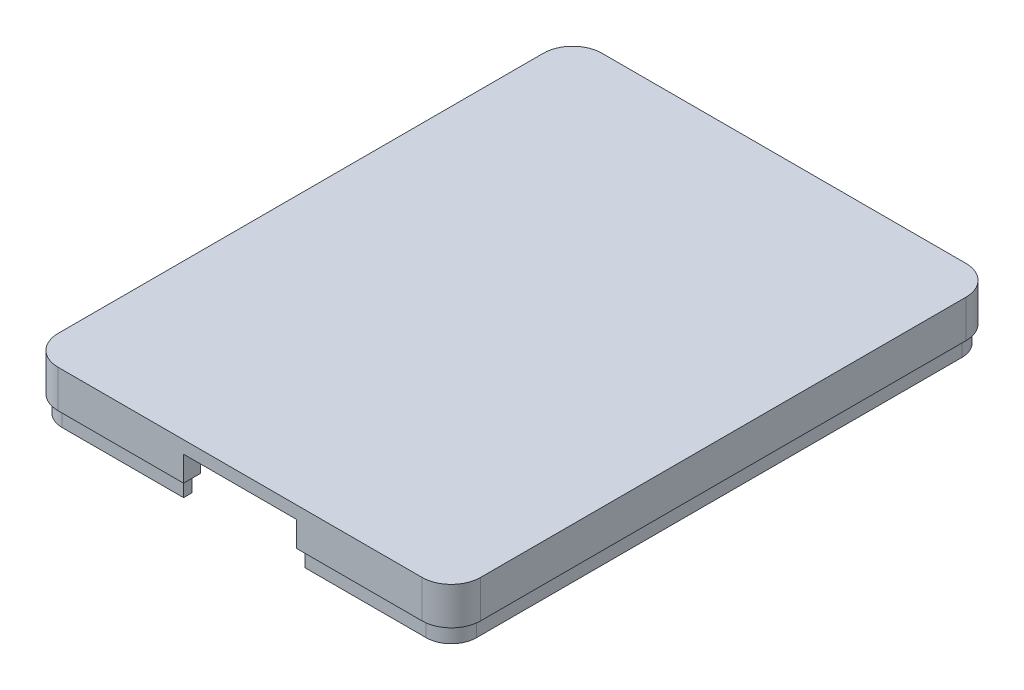
SolidWorks part; units mm, degrees
ref_plane "Alzado" through (0, 0, 0) normal (0, 0, 1) x (1, 0, 0)
ref_plane "Planta" through (0, 0, 0) normal (0, 1, 0) x (1, 0, 0)
ref_plane "Vista lateral" through (0, 0, 0) normal (1, 0, 0) x (0, 0, -1)
sketch "Sketch1" plane through (0, 0, 0) normal (0, 1, 0) x (1, 0, 0)
  line L1 (-21.75, -32.5) -> (21.75, -32.5)
  line L2 (-25.25, -29) -> (-25.25, 29)
  line L3 (-21.75, 32.5) -> (21.75, 32.5)
  line L4 (25.25, -29) -> (25.25, 29)
  line L5 (-25.25, -32.5) -> (25.25, 32.5) construction
  line L6 (-25.25, 32.5) -> (25.25, -32.5) construction
  arc A0 (-21.75, -32.5) -> (-25.25, -29) centre (-21.75, -29) cw
  arc A1 (21.75, -32.5) -> (25.25, -29) centre (21.75, -29) ccw
  arc A2 (-25.25, 29) -> (-21.75, 32.5) centre (-21.75, 29) cw
  arc A3 (21.75, 32.5) -> (25.25, 29) centre (21.75, 29) cw
  point P0 (0, 0)
  dimension "D3" = 3.5
  dimension "D1" = 50.5
  dimension "D2" = 65
extrude "Boss-Extrude1" add sketch "Sketch1" along normal blind 4.5
sketch "Sketch2" plane through (0, 0, 0) normal (0, -1, 0) x (1, 0, 0)
  line L0 (25.25, 29) -> (25.25, -29) construction
  line L1 (-19.75, -30.5) -> (19.75, -30.5)
  line L2 (-23.25, -27) -> (-23.25, 27)
  line L3 (-19.75, 30.5) -> (19.75, 30.5)
  line L4 (23.25, -27) -> (23.25, 27)
  line L5 (-23.25, -30.5) -> (23.25, 30.5) construction
  line L6 (-23.25, 30.5) -> (23.25, -30.5) construction
  line L7 (-21.75, 32.5) -> (21.75, 32.5) construction
  arc A0 (19.75, -30.5) -> (23.25, -27) centre (19.75, -27) ccw
  arc A1 (-19.75, -30.5) -> (-23.25, -27) centre (-19.75, -27) cw
  arc A2 (-23.25, 27) -> (-19.75, 30.5) centre (-19.75, 27) cw
  arc A3 (19.75, 30.5) -> (23.25, 27) centre (19.75, 27) cw
  point P0 (0, 0)
  dimension "D3" = 3.5
  dimension "D1" = 2
  dimension "D2" = 2
extrude "Cut-Extrude1" cut sketch "Sketch2" against normal blind 4
sketch "Sketch3" plane through (0, 0, 32.5) normal (0, 0, 1) x (1, 0, 0)
  line L0 (0, 0) -> (0, 4.5) construction
  line L1 (-21.75, 4.5) -> (21.75, 4.5) construction
  line L3 (-6.75, 3) -> (6.75, 3)
  line L4 (-6.75, 3) -> (-6.75, -3)
  line L5 (-6.75, -3) -> (6.75, -3)
  line L6 (6.75, 3) -> (6.75, -3)
  line L7 (-6.75, 3) -> (6.75, -3) construction
  line L8 (-6.75, -3) -> (6.75, 3) construction
  dimension "D1" = 1.5
  dimension "D2" = 13.5
extrude "Cut-Extrude2" cut sketch "Sketch3" against normal blind 15
curve "CurvaComp1"
curve "CurvaComp2"
sketch "Croquis2" plane through (0, 0, 0) normal (0, -1, 0) x (1, 0, 0)
  line L0 (-6.75, 32.5) -> (-6.75, 30.5) construction
  line L1 (-6.75, 32.5) -> (-6.75, 30.5)
  line L2 (6.75, 30.5) -> (6.75, 32.5) construction
  line L3 (6.75, 30.5) -> (6.75, 32.5)
  line L4 (-21.75, 32.5) -> (-6.75, 32.5) construction
  line L5 (-25.25, -29) -> (-25.25, 29) construction
  line L6 (21.75, -32.5) -> (-21.75, -32.5) construction
  line L7 (25.25, 29) -> (25.25, -29) construction
  line L8 (6.75, 32.5) -> (21.75, 32.5) construction
  line L9 (-21.75, 32.5) -> (-6.75, 32.5)
  line L10 (-25.25, -29) -> (-25.25, 29)
  line L11 (21.75, -32.5) -> (-21.75, -32.5)
  line L12 (25.25, 29) -> (25.25, -29)
  line L13 (6.75, 32.5) -> (21.75, 32.5)
  line L14 (-19.75, 30.5) -> (-6.75, 30.5) construction
  line L15 (-23.25, -27) -> (-23.25, 27) construction
  line L16 (19.75, -30.5) -> (-19.75, -30.5) construction
  line L17 (23.25, 27) -> (23.25, -27) construction
  line L18 (6.75, 30.5) -> (19.75, 30.5) construction
  line L19 (-19.75, 30.5) -> (-6.75, 30.5)
  line L20 (-23.25, -27) -> (-23.25, 27)
  line L21 (19.75, -30.5) -> (-19.75, -30.5)
  line L22 (23.25, 27) -> (23.25, -27)
  line L23 (6.75, 30.5) -> (19.75, 30.5)
  arc A0 (-21.75, 32.5) -> (-25.25, 29) centre (-21.75, 29) ccw construction
  arc A1 (-25.25, -29) -> (-21.75, -32.5) centre (-21.75, -29) ccw construction
  arc A2 (21.75, -32.5) -> (25.25, -29) centre (21.75, -29) ccw construction
  arc A3 (25.25, 29) -> (21.75, 32.5) centre (21.75, 29) ccw construction
  arc A4 (-21.75, 32.5) -> (-25.25, 29) centre (-21.75, 29) ccw
  arc A5 (-25.25, -29) -> (-21.75, -32.5) centre (-21.75, -29) ccw
  arc A6 (21.75, -32.5) -> (25.25, -29) centre (21.75, -29) ccw
  arc A7 (25.25, 29) -> (21.75, 32.5) centre (21.75, 29) ccw
  arc A8 (-19.75, 30.5) -> (-23.25, 27) centre (-19.75, 27) ccw construction
  arc A9 (-23.25, -27) -> (-19.75, -30.5) centre (-19.75, -27) ccw construction
  arc A10 (19.75, -30.5) -> (23.25, -27) centre (19.75, -27) ccw construction
  arc A11 (23.25, 27) -> (19.75, 30.5) centre (19.75, 27) ccw construction
  arc A12 (-19.75, 30.5) -> (-23.25, 27) centre (-19.75, 27) ccw
  arc A13 (-23.25, -27) -> (-19.75, -30.5) centre (-19.75, -27) ccw
  arc A14 (19.75, -30.5) -> (23.25, -27) centre (19.75, -27) ccw
  arc A15 (23.25, 27) -> (19.75, 30.5) centre (19.75, 27) ccw
sketch "Croquis3" plane through (0, 0, 0) normal (0, -1, 0) x (1, 0, 0)
  line L24 (-24.75, 29) -> (-24.75, -29)
  line L25 (-7.25, 32) -> (-21.75, 32)
  line L26 (-7.25, 31) -> (-7.25, 32)
  line L27 (-19.75, 31) -> (-7.25, 31)
  line L28 (-23.75, -27) -> (-23.75, 27)
  line L29 (19.75, -31) -> (-19.75, -31)
  line L30 (23.75, 27) -> (23.75, -27)
  line L31 (7.25, 31) -> (19.75, 31)
  line L32 (7.25, 32) -> (7.25, 31)
  line L33 (21.75, 32) -> (7.25, 32)
  line L34 (24.75, -29) -> (24.75, 29)
  line L35 (-21.75, -32) -> (21.75, -32)
  line L36 (-24.75, 29) -> (-24.75, -29)
  line L37 (-7.25, 32) -> (-21.75, 32)
  line L38 (-7.25, 31) -> (-7.25, 32)
  line L39 (-19.75, 31) -> (-7.25, 31)
  line L40 (-23.75, -27) -> (-23.75, 27)
  line L41 (19.75, -31) -> (-19.75, -31)
  line L42 (23.75, 27) -> (23.75, -27)
  line L43 (7.25, 31) -> (19.75, 31)
  line L44 (7.25, 32) -> (7.25, 31)
  line L45 (21.75, 32) -> (7.25, 32)
  line L46 (24.75, -29) -> (24.75, 29)
  line L47 (-21.75, -32) -> (21.75, -32)
  arc A16 (-21.75, 32) -> (-24.75, 29) centre (-21.75, 29) ccw
  arc A17 (-19.75, 31) -> (-23.75, 27) centre (-19.75, 27) ccw
  arc A18 (-23.75, -27) -> (-19.75, -31) centre (-19.75, -27) ccw
  arc A19 (19.75, -31) -> (23.75, -27) centre (19.75, -27) ccw
  arc A20 (23.75, 27) -> (19.75, 31) centre (19.75, 27) ccw
  arc A21 (24.75, 29) -> (21.75, 32) centre (21.75, 29) ccw
  arc A22 (21.75, -32) -> (24.75, -29) centre (21.75, -29) ccw
  arc A23 (-24.75, -29) -> (-21.75, -32) centre (-21.75, -29) ccw
  arc A24 (-21.75, 32) -> (-24.75, 29) centre (-21.75, 29) ccw
  arc A25 (-19.75, 31) -> (-23.75, 27) centre (-19.75, 27) ccw
  arc A26 (-23.75, -27) -> (-19.75, -31) centre (-19.75, -27) ccw
  arc A27 (19.75, -31) -> (23.75, -27) centre (19.75, -27) ccw
  arc A28 (23.75, 27) -> (19.75, 31) centre (19.75, 27) ccw
  arc A29 (24.75, 29) -> (21.75, 32) centre (21.75, 29) ccw
  arc A30 (21.75, -32) -> (24.75, -29) centre (21.75, -29) ccw
  arc A31 (-24.75, -29) -> (-21.75, -32) centre (-21.75, -29) ccw
  dimension "D1" = 0.5
extrude "Saliente-Extruir1" add sketch "Croquis3" along normal blind 2
